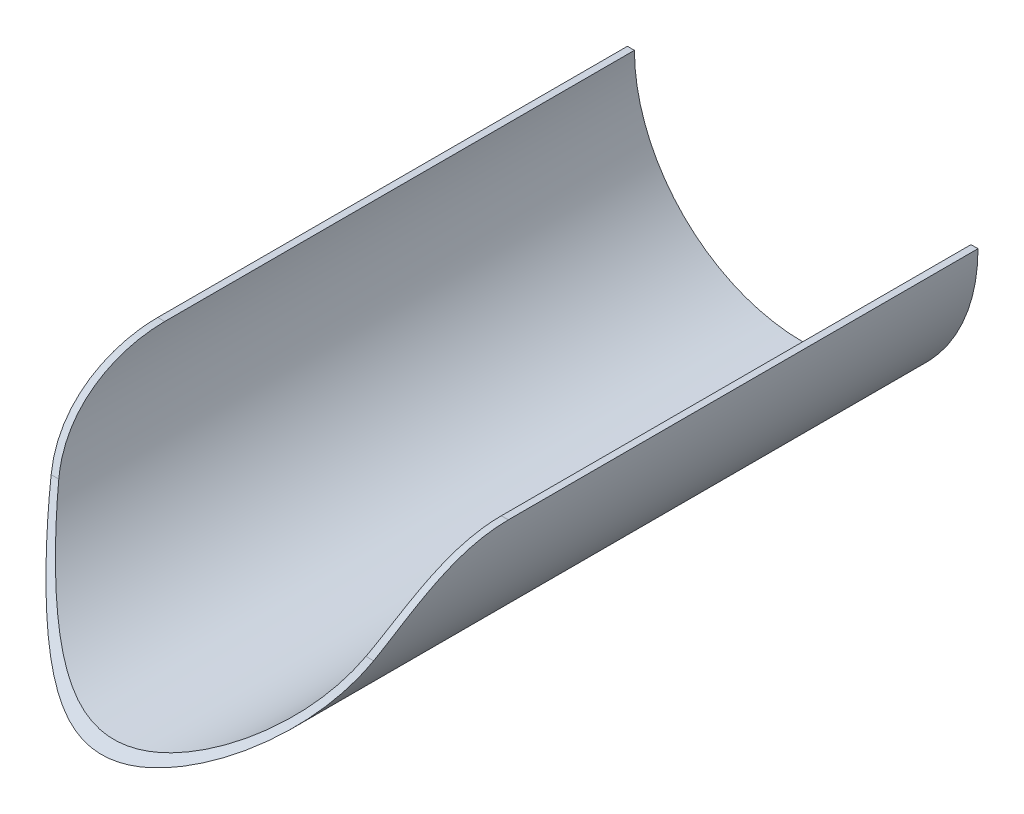
SolidWorks part; units mm, degrees
material "PLA"
ref_plane "Front Plane" through (0, 0, 0) normal (0, 0, 1) x (1, 0, 0)
ref_plane "Top Plane" through (0, 0, 0) normal (0, 1, 0) x (1, 0, 0)
ref_plane "Right Plane" through (0, 0, 0) normal (1, 0, 0) x (0, 0, -1)
sketch "Sketch1" plane through (0, 0, 0) normal (0, 0, 1) x (1, 0, 0)
  line L0 (-64.0179, 0) -> (70.1786, 0) construction
  arc A0 (-50, 0) -> (50, 0) centre (0, 0) ccw
  dimension "D1" = 100
extrude "Extrude-Thin1" add sketch "Sketch1" against normal blind 200 thin thin type one direction reverse wall 2
sketch "Sketch2" plane through (0, 0, 0) normal (1, 0, 0) x (0, 0, -1)
  line L1 (0, 0) -> (0, -50) construction
  line L2 (0, 0) -> (0, -50)
  line L4 (200, 0) -> (0, 0) construction
  line L5 (0, 0) -> (40, 0)
  arc A0 (0, -50) -> (40, 0) centre (-38.9491, 22.1593) ccw
  dimension "D2" = 82
  dimension "D1" = 40
extrude "Cut-Extrude1" cut sketch "Sketch2" against normal through all both and the other way through all
fillet "Fillet1" radius 40 2 edges at (49, 0, -40) (-49, 0, -40)
